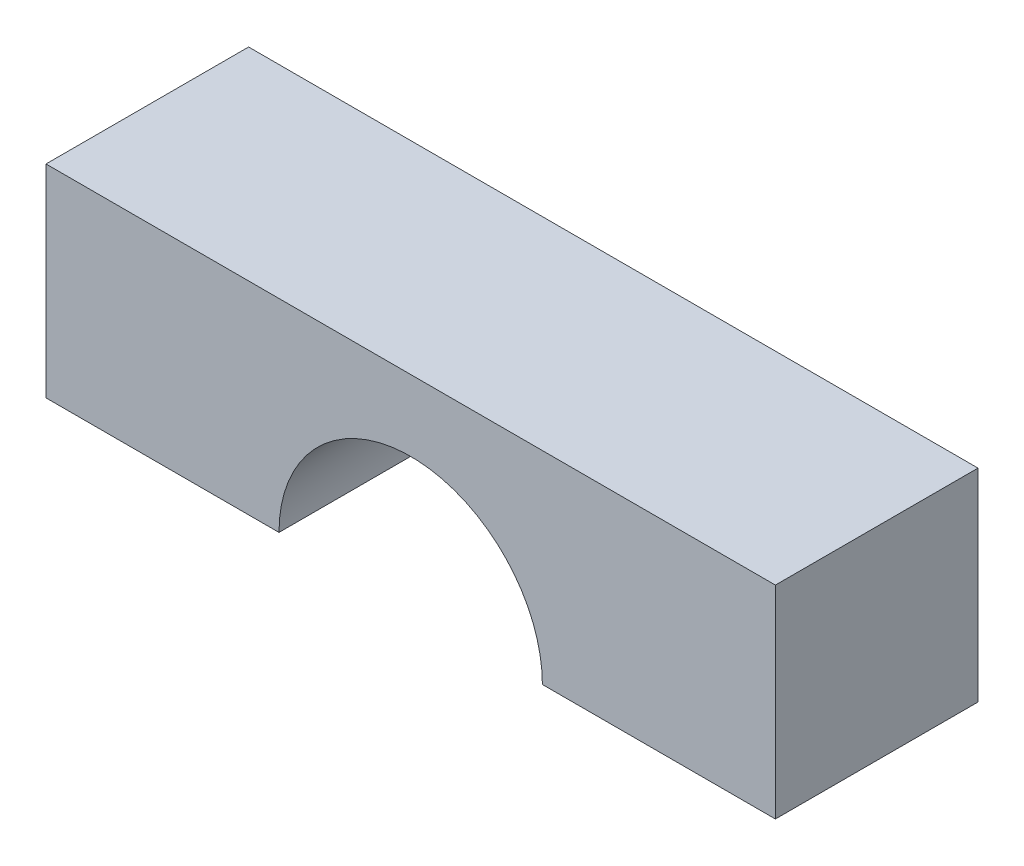
SolidWorks part; units mm, degrees
ref_plane "Front Plane" through (0, 0, 0) normal (0, 0, 1) x (1, 0, 0)
ref_plane "Top Plane" through (0, 0, 0) normal (0, 1, 0) x (1, 0, 0)
ref_plane "Right Plane" through (0, 0, 0) normal (1, 0, 0) x (0, 0, -1)
sketch "Sketch1" plane through (0, 0, 0) normal (0, 0, 1) x (1, 0, 0)
  line L0 (0, 0) -> (0, 5) construction
  line L1 (3.25, 0) -> (9, 0)
  line L2 (9, 0) -> (9, 5)
  line L3 (9, 5) -> (-9, 5)
  line L4 (-9, 0) -> (-9, 5)
  line L5 (-3.25, 0) -> (-9, 0)
  arc A0 (3.25, 0) -> (-3.25, 0) centre (0, 0) ccw
  dimension "D3" = 3.25
  dimension "D1" = 18
  dimension "D2" = 5
extrude "Boss-Extrude1" add sketch "Sketch1" along normal blind 5
